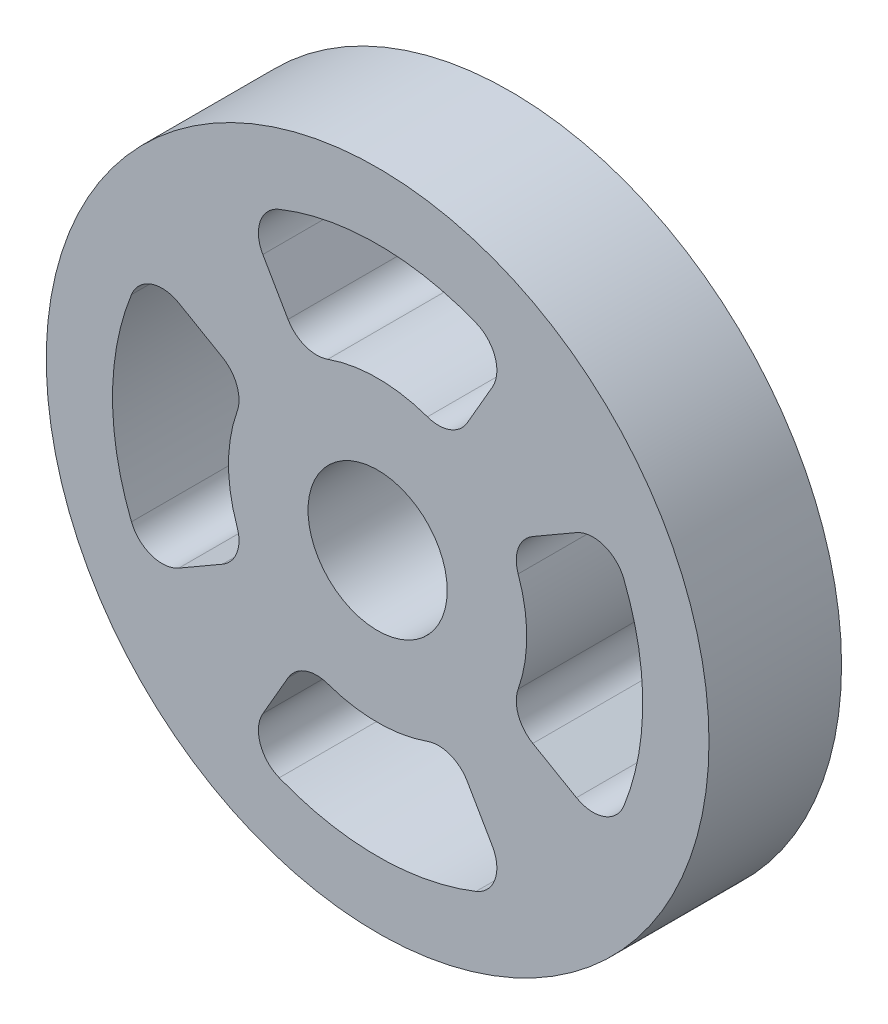
SolidWorks part; units mm, degrees
ref_plane "Front Plane" through (0, 0, 0) normal (0, 0, 1) x (1, 0, 0)
ref_plane "Top Plane" through (0, 0, 0) normal (0, 1, 0) x (1, 0, 0)
ref_plane "Right Plane" through (0, 0, 0) normal (1, 0, 0) x (0, 0, -1)
sketch "Sketch1" plane through (0, 0, 0) normal (0, 0, 1) x (1, 0, 0)
  circle A0 centre (0, 0) radius 21
  circle A1 centre (0, 0) radius 30
  dimension "D1" = 42
  dimension "D2" = 60
extrude "Boss-Extrude1" add sketch "Sketch1" along normal blind 20 and the other way blind 20
sketch "Sketch2" plane through (0, 0, 0) normal (0, 0, 1) x (1, 0, 0)
  circle A0 centre (0, 0) radius 100
  circle A1 centre (0, 0) radius 21
  dimension "D1" = 200
extrude "Boss-Extrude2" add sketch "Sketch2" along normal blind 20 and the other way blind 20
sketch "Sketch3" plane through (0, 0, 0) normal (0, 0, 1) x (1, 0, 0)
  line L2 (0, -106.687) -> (0, 119.8676) construction
  line L3 (-27.0416, 46.8375) -> (-34.641, 60)
  line L4 (27.0416, 46.8375) -> (34.641, 60)
  line L5 (46.8375, 27.0416) -> (60, 34.641)
  line L6 (46.8375, -27.0416) -> (60, -34.641)
  line L7 (27.0416, -46.8375) -> (34.641, -60)
  line L8 (-27.0416, -46.8375) -> (-34.641, -60)
  line L9 (-46.8375, -27.0416) -> (-60, -34.641)
  line L10 (-46.8375, 27.0416) -> (-60, 34.641)
  arc A0 (-29.6923, 74.2857) -> (29.6923, 74.2857) centre (0, 0) cw
  arc A1 (-15.0393, 42.4125) -> (15.0393, 42.4125) centre (0, 0) cw
  arc A2 (34.641, 60) -> (29.6923, 74.2857) centre (25.9808, 65) ccw
  arc A3 (-34.641, 60) -> (-29.6923, 74.2857) centre (-25.9808, 65) cw
  arc A4 (-15.0393, 42.4125) -> (-27.0416, 46.8375) centre (-18.3814, 51.8375) cw
  arc A5 (15.0393, 42.4125) -> (27.0416, 46.8375) centre (18.3814, 51.8375) ccw
  arc A6 (74.2857, 29.6923) -> (74.2857, -29.6923) centre (0, 0) cw
  arc A7 (42.4125, 15.0393) -> (42.4125, -15.0393) centre (0, 0) cw
  arc A8 (60, -34.641) -> (74.2857, -29.6923) centre (65, -25.9808) ccw
  arc A9 (60, 34.641) -> (74.2857, 29.6923) centre (65, 25.9808) cw
  arc A10 (42.4125, 15.0393) -> (46.8375, 27.0416) centre (51.8375, 18.3814) cw
  arc A11 (42.4125, -15.0393) -> (46.8375, -27.0416) centre (51.8375, -18.3814) ccw
  arc A12 (29.6923, -74.2857) -> (-29.6923, -74.2857) centre (0, 0) cw
  arc A13 (15.0393, -42.4125) -> (-15.0393, -42.4125) centre (0, 0) cw
  arc A14 (-34.641, -60) -> (-29.6923, -74.2857) centre (-25.9808, -65) ccw
  arc A15 (34.641, -60) -> (29.6923, -74.2857) centre (25.9808, -65) cw
  arc A16 (15.0393, -42.4125) -> (27.0416, -46.8375) centre (18.3814, -51.8375) cw
  arc A17 (-15.0393, -42.4125) -> (-27.0416, -46.8375) centre (-18.3814, -51.8375) ccw
  arc A18 (-74.2857, -29.6923) -> (-74.2857, 29.6923) centre (0, 0) cw
  arc A19 (-42.4125, -15.0393) -> (-42.4125, 15.0393) centre (0, 0) cw
  arc A20 (-60, 34.641) -> (-74.2857, 29.6923) centre (-65, 25.9808) ccw
  arc A21 (-60, -34.641) -> (-74.2857, -29.6923) centre (-65, -25.9808) cw
  arc A22 (-42.4125, -15.0393) -> (-46.8375, -27.0416) centre (-51.8375, -18.3814) cw
  arc A23 (-42.4125, 15.0393) -> (-46.8375, 27.0416) centre (-51.8375, 18.3814) ccw
  point P10 (40, 69.282)
  point P13 (-40, 69.282)
  point P16 (-22.5, 38.9711)
  point P19 (22.5, 38.9711)
  point P59 (0, 0)
  dimension "D1" = 80
  dimension "D3" = 45
  dimension "D7" = 10
  dimension "D2" = 60
  dimension "D4" = 60
  dimension "D5" = 40
  dimension "D6" = 22.5
  dimension "D8" = 4
extrude "Cut-Extrude1" cut sketch "Sketch3" against normal blind 20 and the other way blind 20
